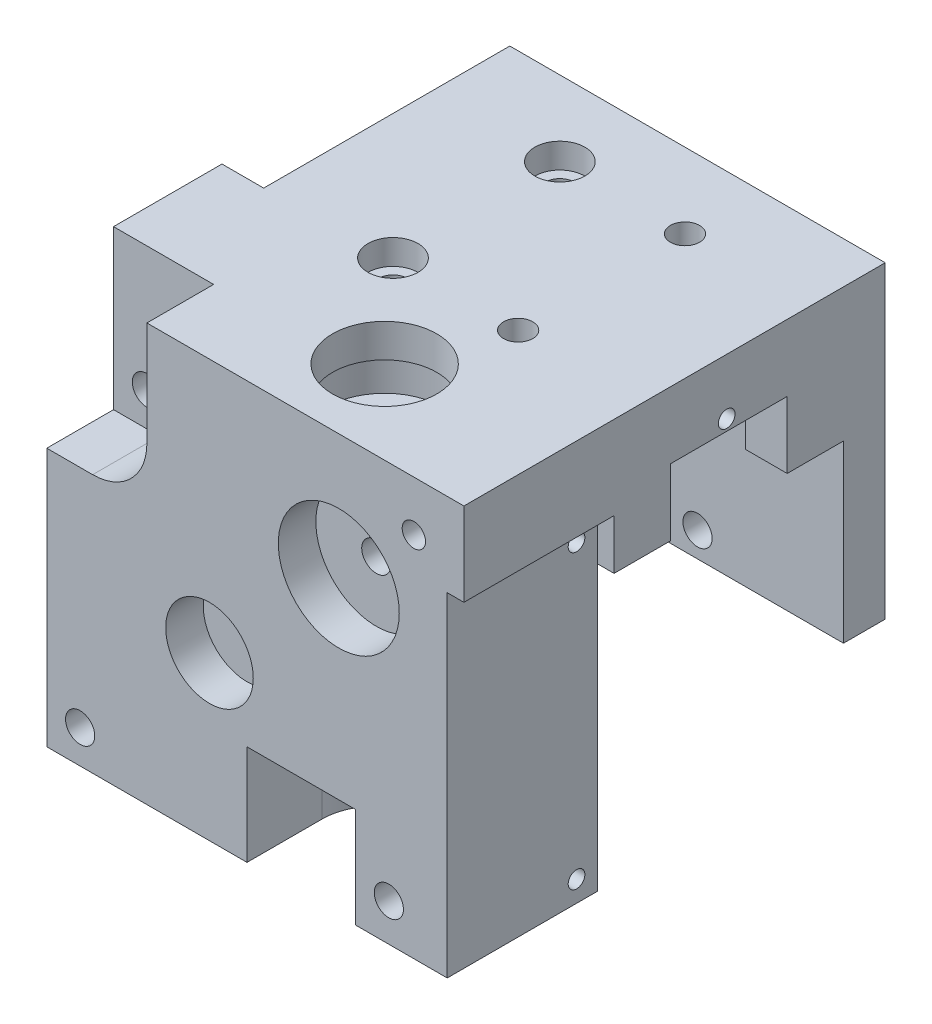
SolidWorks part; units mm, degrees
material "ABS"
ref_plane "Front Plane" through (0, 0, 0) normal (0, 0, 1) x (1, 0, 0)
ref_plane "Top Plane" through (0, 0, 0) normal (0, 1, 0) x (1, 0, 0)
ref_plane "Right Plane" through (0, 0, 0) normal (1, 0, 0) x (0, 0, -1)
sketch "Sketch1" plane through (0, 0, 0) normal (0, 1, 0) x (1, 0, 0)
  line L1 (-17.5, -14) -> (17.5, -14)
  line L2 (-17.5, -14) -> (-17.5, 14)
  line L3 (-17.5, 14) -> (17.5, 14)
  line L4 (17.5, -14) -> (17.5, 14)
  line L5 (-17.5, -14) -> (17.5, 14) construction
  line L6 (-17.5, 14) -> (17.5, -14) construction
  point P0 (0, 0)
  dimension "D1" = 28
  dimension "D2" = 35
extrude "Boss-Extrude1" add sketch "Sketch1" along normal blind 4
sketch "Sketch2" plane through (0, 4, 0) normal (0, 1, 0) x (1, 0, 0)
  line L0 (-17.5, -14) -> (17.5, -14) construction
  line L1 (-17.5, 14) -> (-17.5, -14) construction
  line L2 (-17.5, -14) -> (17.5, -14) construction
  line L3 (17.5, 14) -> (-17.5, 14) construction
  circle A0 centre (-7.5, -10) radius 1.75
  circle A1 centre (-7.5, 10) radius 1.75
  circle A2 centre (7.5, -10) radius 1.75
  circle A3 centre (7.5, 10) radius 1.75
  dimension "D1" = 3.5
  dimension "D2" = 3.5
  dimension "D5" = 3.5
  dimension "D8" = 3.5
  dimension "D3" = 20
  dimension "D4" = 4
  dimension "D6" = 15
  dimension "D7" = 10
  dimension "D9" = 15
  dimension "D10" = 4
  dimension "D11" = 4
extrude "Cut-Extrude1" cut sketch "Sketch2" against normal through all
sketch "Sketch3" plane through (0, 0, 14) normal (0, 0, 1) x (1, 0, 0)
  line L0 (17.5, 4) -> (17.5, 0) construction
  line L1 (-17.5, 4) -> (17.5, 4)
  line L2 (-17.5, 4) -> (-17.5, -46)
  line L3 (-17.5, -46) -> (17.5, -46)
  line L4 (17.5, 4) -> (17.5, -46)
  dimension "D1" = 50
extrude "Boss-Extrude2" add sketch "Sketch3" along normal blind 17.5 and the other way blind 0.5
sketch "Sketch7" plane through (0, 0, -14) normal (0, 0, -1) x (-1, 0, 0)
  line L1 (-17.5, 4) -> (17.5, 4)
  line L2 (-17.5, 4) -> (-17.5, -33)
  line L3 (-17.5, -33) -> (17.5, -33)
  line L4 (17.5, 4) -> (17.5, -33)
  line L6 (17.5, 4) -> (17.5, 0) construction
  dimension "D1" = 37
extrude "Boss-Extrude3" add sketch "Sketch7" along normal blind 5
sketch "Sketch10" plane through (0, 0, -19) normal (0, 0, -1) x (-1, 0, 0)
  line L1 (0, 4) -> (0, -33) construction
  line L3 (17.5, 4) -> (-17.5, 4) construction
  line L4 (-17.5, -33) -> (17.5, -33) construction
  circle A1 centre (-5, -30) radius 1.75
  circle A2 centre (5, -30) radius 1.75
  dimension "D1" = 3
  dimension "D2" = 3.5
  dimension "D4" = 3.5
  dimension "D3" = 5
  dimension "D5" = 5
extrude "Cut-Extrude6" cut sketch "Sketch10" against normal blind 5
sketch "Sketch18" plane through (0, 4, 0) normal (0, 1, 0) x (1, 0, 0)
  line L0 (-17.5, -10) -> (-10.5, -10)
  line L1 (-17.5, 19) -> (-17.5, -31.5) construction
  line L2 (-10.5, -10) -> (-10.5, -11.5)
  line L3 (-10.5, -11.5) -> (-17.5, -11.5)
  line L4 (-17.5, -11.5) -> (-17.5, -10)
  line L5 (17.5, 10) -> (10.5, 10)
  line L6 (17.5, -31.5) -> (17.5, 19) construction
  line L7 (10.5, 10) -> (10.5, 11.5)
  line L8 (10.5, 11.5) -> (17.5, 11.5)
  line L9 (17.5, 11.5) -> (17.5, 10)
  circle A0 centre (-7.5, -10) radius 1.75 construction
  circle A1 centre (7.5, 10) radius 1.75 construction
  dimension "D4" = 3
  dimension "D1" = 0
  dimension "D2" = 3
  dimension "D3" = 1.5
  dimension "D5" = 0
  dimension "D6" = 1.5
extrude "Cut-Extrude14" [suppressed] cut sketch "Sketch18" against normal through all
sketch "Sketch19" plane through (0, 4, 0) normal (0, 1, 0) x (1, 0, 0)
  line L0 (-17.5, 19) -> (-17.5, -31.5) construction
  line L1 (17.5, -31.5) -> (17.5, 19) construction
  circle A0 centre (-7.5, 0) radius 1.75
  circle A1 centre (7.5, 0) radius 1.75
  dimension "D3" = 3.5
  dimension "D4" = 3.5
  dimension "D1" = 10
  dimension "D2" = 10
extrude "Cut-Extrude15" [suppressed] cut sketch "Sketch19" against normal through all
sketch "Sketch20" [suppressed] plane through (0, 0, 0) normal (0, -1, 0) x (1, 0, 0)
  line L1 (10.9641, 0) -> (9.2321, 3)
  line L2 (9.2321, 3) -> (5.7679, 3)
  line L3 (5.7679, 3) -> (4.0359, 0)
  line L4 (4.0359, 0) -> (5.7679, -3)
  line L5 (5.7679, -3) -> (9.2321, -3)
  line L6 (9.2321, -3) -> (10.9641, 0)
  line L7 (-10.9641, 0) -> (-9.2321, -3)
  line L8 (-9.2321, -3) -> (-5.7679, -3)
  line L9 (-5.7679, -3) -> (-4.0359, 0)
  line L10 (-4.0359, 0) -> (-5.7679, 3)
  line L11 (-5.7679, 3) -> (-9.2321, 3)
  line L12 (-9.2321, 3) -> (-10.9641, 0)
  circle A0 centre (7.5, 0) radius 3 construction
  circle A1 centre (-7.5, 0) radius 3 construction
  dimension "D1" = 6
  dimension "D2" = 6
extrude "Cut-Extrude16" [suppressed] cut sketch "Sketch20" against normal blind 3
sketch "Sketch21" [suppressed] plane through (0, 4, 0) normal (0, 1, 0) x (1, 0, 0)
  line L0 (-10.5, -10) -> (-17.5, -10) construction
  circle A0 centre (-17, -10) radius 0.5
  dimension "D1" = 1
extrude "Cut-Extrude17" [suppressed] cut sketch "Sketch21" against normal blind 4
pattern_linear "LPattern2" [suppressed] count 4 spacing 2 of bodies 121
fillet "Fillet2" [suppressed] radius 0.15
sketch "Sketch24" plane through (-17.5, 0, 0) normal (-1, 0, 0) x (0, 0, 1)
  line L5 (31.5, -46) -> (13.5, -46) construction
  line L6 (13.5, -46) -> (31.5, -46)
  line L7 (13.5, -46) -> (13.5, 0)
  line L8 (13.5, 0) -> (31.5, 0)
  line L9 (31.5, -46) -> (31.5, 0)
  line L10 (13.5, 0) -> (13.5, -46) construction
  line L11 (31.5, 4) -> (31.5, -46) construction
extrude "Boss-Extrude4" add sketch "Sketch24" along normal blind 10
sketch "Sketch37" plane through (-17.5, 0, 0) normal (-1, 0, 0) x (0, 0, 1)
  line L1 (10.5, 4) -> (23.5, 4)
  line L2 (10.5, 4) -> (10.5, -10)
  line L3 (10.5, -10) -> (23.5, -10)
  line L4 (23.5, 4) -> (23.5, -10)
  dimension "D1" = 3
  dimension "D2" = 10
  dimension "D3" = 14
extrude "Boss-Extrude9" add sketch "Sketch37" along normal blind 10
sketch "Sketch22" plane through (0, 0, 31.5) normal (0, 0, 1) x (1, 0, 0)
  line L0 (-27.5, -46) -> (-27.5, 0) construction
  line L1 (-15.5, 0) -> (-27.5, 0)
  line L2 (-27.5, -46) -> (17.5, -46) construction
  line L4 (-27.5, 0) -> (-17.5, 0) construction
  line L5 (-27.5, -46) -> (17.5, -46) construction
  line L6 (-27.5, 0) -> (-27.5, -15)
  line L9 (-27.5, -15) -> (-22, -15)
  line L10 (-15.5, 0) -> (-15.5, -8.5)
  line L11 (9.5, -46) -> (-3.5, -46)
  line L12 (9.5, -46) -> (9.5, -34)
  line L13 (9.5, -34) -> (-3.5, -34)
  line L14 (-3.5, -46) -> (-3.5, -34)
  line L16 (-15.5, 0) -> (-17.5, 0)
  line L17 (-15.5, 0) -> (-15.5, 4)
  line L18 (-15.5, 4) -> (-17.5, 4)
  line L19 (-17.5, 0) -> (-17.5, 4)
  circle A0 centre (-23.5, -42) radius 1.75
  circle A1 centre (13.5, -41.5) radius 1.75
  circle A3 centre (7.5, -11) radius 7.25
  circle A4 centre (-8, -26.5) radius 5.25
  arc A5 (-22, -15) -> (-15.5, -8.5) centre (-22, -8.5) ccw
  circle A6 centre (7.5, -11) radius 1.75
  circle A7 centre (-23.5, -11) radius 1.75
  point P21 (-15.5, -15)
  line M3 (-17.5, 4) -> (-17.5, 0)
  line M6 (17.5, 4) -> (-17.5, 4)
  line M24 (-17.5, 0) -> (-27.5, 0)
  line M25 (-27.5, 0) -> (-27.5, -46)
  dimension "D3" = 3.5
  dimension "D6" = 35
  dimension "D7" = 3.5
  dimension "D9" = 14.5
  dimension "D11" = 10.5
  dimension "D15" = 6.5
  dimension "D22" = 3.5
  dimension "D23" = 3.5
  dimension "D2" = 4
  dimension "D4" = 4.5
  dimension "D5" = 4
  dimension "D8" = 12
  dimension "D10" = 35
  dimension "D12" = 19.5
  dimension "D13" = 19.5
  dimension "D14" = 31
  dimension "D16" = 24
  dimension "D17" = 13
  dimension "D18" = 12
  dimension "D19" = 41
  dimension "D20" = 4
  dimension "D21" = 35
extrude "Cut-Extrude19" cut sketch "Sketch22" against normal up to next contours A0 | A1 | A7 | A6 region at (-23.5, -42, 31.5) region at (13.5, -41.5, 31.5) region at (7.5, -11, 31.5) region at (-23.5, -11, 31.5)
extrude "Cut-Extrude20" cut sketch "Sketch22<3>" against normal blind 4.5 contours A3 | A4
sketch "Sketch22<3>" plane through (0, 0, 31.5) normal (0, 0, 1) x (1, 0, 0) same geometry as "Sketch22"
extrude "Cut-Extrude24" cut sketch "Sketch22<5>" against normal blind 8 contours L9 A5 L10 L1 A7 M24 M25 | L1 L17 M6 M3 region at (-21.6364, -6.9513, 31.5) region at (-16.5, 2, 31.5)
sketch "Sketch22<5>" plane through (0, 0, 31.5) normal (0, 0, 1) x (1, 0, 0) same geometry as "Sketch22"
extrude "Cut-Extrude21" cut sketch "Sketch22<4>" against normal blind 15.5 contours L14 L13 L12 L11
sketch "Sketch22<4>" plane through (0, 0, 31.5) normal (0, 0, 1) x (1, 0, 0) same geometry as "Sketch22"
fillet "Fillet3" radius 6.5 2 edges at (9.5, -40, 16) (-3.5, -40, 16)
sketch "Sketch26" plane through (0, -34, 0) normal (0, -1, 0) x (1, 0, 0)
  line L0 (9.5, 31.5) -> (-3.5, 31.5) construction
  line L1 (-3.5, 22.5) -> (-3.5, 31.5) construction
  circle A0 centre (3, 21.5) radius 2.25
  dimension "D1" = 4.5
  dimension "D2" = 10
  dimension "D3" = 6.5
extrude "Cut-Extrude22" cut sketch "Sketch26" against normal through all
sketch "Sketch27" plane through (0, 4, 0) normal (0, 1, 0) x (1, 0, 0)
  circle A0 centre (3, -21.5) radius 6.25
  dimension "D1" = 12.5
extrude "Cut-Extrude23" cut sketch "Sketch27" against normal blind 8
sketch "Sketch41" plane through (-27.5, 0, 0) normal (-1, 0, 0) x (0, 0, 1)
  line L0 (13.5, -10) -> (13.5, -46) construction
  line L1 (13.5, -46) -> (31.5, -46) construction
  line L2 (20.5, -42.5) -> (20.5, -39)
  line L15 (23, -42.5) -> (23, -39)
  line L16 (17, -46) -> (17, -48.5)
  line L17 (20.5, -39) -> (23, -39)
  line L18 (17, -46) -> (21.8734, -46)
  circle A0 centre (17, -42.5) radius 1.25
  arc A1 (17, -46) -> (20.5, -42.5) centre (17, -42.5) ccw
  arc A2 (17, -48.5) -> (23, -42.5) centre (17, -42.5) ccw
  line M16 (13.5, -46) -> (31.5, -46)
  dimension "D5" = 2.5
  dimension "D1" = 3.5
  dimension "D2" = 3.5
  dimension "D3" = 3.5
  dimension "D4" = 2.5
extrude "Boss-Extrude10" [suppressed] add sketch "Sketch41" along normal blind 2.5 contours A0 | A2 L15 L17 L2 A1 M16
sketch "Sketch43" plane through (17.5, 0, 0) normal (1, 0, 0) x (0, 0, -1)
  line L0 (-31.5, -46) -> (-31.5, 4)
  line L1 (-31.5, 4) -> (19, 4)
  line L2 (19, 4) -> (19, -33)
  line L3 (19, -33) -> (14, -33)
  line L6 (-13.5, 0) -> (14, 0) construction
  line L7 (-31.5, -46) -> (-13.5, -46)
  line L11 (-6.75, -4) -> (-6.75, -12)
  line L12 (-6.75, -12) -> (-13.5, -12)
  line L13 (7.25, -4) -> (7.25, -12)
  line L14 (7.25, -12) -> (14, -12)
  line L15 (-6.75, -4) -> (7.25, -4)
  line L16 (-13.5, -12) -> (-13.5, -46)
  line L17 (14, -12) -> (14, -33)
  dimension "D1" = 29
  dimension "D3" = 6.75
  dimension "D4" = 12
  dimension "D5" = 14
extrude "Boss-Extrude11" add sketch "Sketch43" along normal blind 5
sketch "Sketch44" plane through (-17.5, 0, 0) normal (-1, 0, 0) x (0, 0, 1)
  line L0 (10.5, 4) -> (-19, 4)
  line L1 (-19, 4) -> (-19, -33)
  line L2 (-19, -33) -> (-14, -33)
  line L8 (-14, -33) -> (-14, -12)
  line L9 (-14, -12) -> (-7.25, -12)
  line L10 (-7.25, -12) -> (-7.25, -4)
  line L11 (-7.25, -4) -> (6.75, -4)
  line L12 (6.75, -4) -> (6.75, -12)
  line L16 (6.75, -12) -> (13.5, -12)
  line L17 (13.5, -12) -> (13.5, -10)
  line L18 (13.5, -10) -> (10.5, -10)
  line L19 (10.5, -10) -> (10.5, 4)
extrude "Boss-Extrude12" add sketch "Sketch44" along normal blind 5
sketch "Sketch29" plane through (0, 0, 13.5) normal (0, 0, -1) x (-1, 0, 0)
  line L1 (-4.1514, -11) -> (-5.8257, -8.1)
  line L2 (-5.8257, -8.1) -> (-9.1743, -8.1)
  line L3 (-9.1743, -8.1) -> (-10.8486, -11)
  line L4 (-10.8486, -11) -> (-9.1743, -13.9)
  line L5 (-9.1743, -13.9) -> (-5.8257, -13.9)
  line L6 (-5.8257, -13.9) -> (-4.1514, -11)
  line L7 (20.1514, -11) -> (21.8257, -13.9)
  line L8 (21.8257, -13.9) -> (25.1743, -13.9)
  line L9 (25.1743, -13.9) -> (26.8486, -11)
  line L10 (26.8486, -11) -> (25.1743, -8.1)
  line L11 (25.1743, -8.1) -> (21.8257, -8.1)
  line L12 (21.8257, -8.1) -> (20.1514, -11)
  line L13 (-10.1514, -41.5) -> (-11.8257, -38.6)
  line L14 (-11.8257, -38.6) -> (-15.1743, -38.6)
  line L15 (-15.1743, -38.6) -> (-16.8486, -41.5)
  line L16 (-16.8486, -41.5) -> (-15.1743, -44.4)
  line L17 (-15.1743, -44.4) -> (-11.8257, -44.4)
  line L18 (-11.8257, -44.4) -> (-10.1514, -41.5)
  line L25 (23.5, -45.3486) -> (26.4, -43.6743)
  line L26 (26.4, -43.6743) -> (26.4, -40.3257)
  line L27 (26.4, -40.3257) -> (23.5, -38.6514)
  line L28 (23.5, -38.6514) -> (20.6, -40.3257)
  line L29 (20.6, -40.3257) -> (20.6, -43.6743)
  line L30 (20.6, -43.6743) -> (23.5, -45.3486)
  circle A0 centre (-7.5, -11) radius 2.9 construction
  circle A1 centre (23.5, -11) radius 2.9 construction
  circle A2 centre (-13.5, -41.5) radius 2.9 construction
  circle A3 centre (23.5, -42) radius 2.9 construction
  dimension "D1" = 5.8
  dimension "D2" = 5.8
  dimension "D3" = 5.8
  dimension "D4" = 5.8
extrude "Cut-Extrude25" cut sketch "Sketch29" against normal blind 3 and the other way up to surface (6.75 mm away) other way up to face at (-20, -8, 6.75)
sketch "Sketch30" plane through (0, 4, 0) normal (0, 1, 0) x (1, 0, 0)
  circle A0 centre (-7.5, 10) radius 3
  circle A1 centre (-7.5, -10) radius 3
  dimension "D1" = 6
  dimension "D2" = 6
extrude "Cut-Extrude26" cut sketch "Sketch30" against normal blind 3
ref_plane "Plane1" [suppressed] through (0, 0, 0) normal (-1, 0, 0) x (0, 0, 1)
sketch "Sketch38" plane through (0, -4, 0) normal (0, 1, 0) x (1, 0, 0)
  circle A0 centre (3, -21.5) radius 7
  dimension "D1" = 14
extrude "Cut-Extrude31" cut sketch "Sketch38" along normal blind 4
sketch "Sketch39" plane through (-27.5, 0, 0) normal (-1, 0, 0) x (0, 0, 1)
  line L0 (13.5, -46) -> (17, -46)
  line L1 (13.5, -46) -> (31.5, -46) construction
  line L2 (13.5, -46) -> (13.5, -19)
  line L3 (13.5, -10) -> (13.5, -46) construction
  line L4 (13.5, -19) -> (17, -19)
  line L5 (20.5, -22.5) -> (20.5, -26)
  line L6 (20.5, -26) -> (27.5, -26)
  line L7 (27.5, -26) -> (27.5, -39)
  line L8 (27.5, -39) -> (20.5, -39)
  line L9 (20.5, -39) -> (20.5, -42.5)
  line L11 (27.5, -29) -> (23.5, -29)
  line L12 (27.5, -29) -> (27.5, -36)
  line L13 (27.5, -36) -> (23.5, -36)
  line L14 (23.5, -29) -> (23.5, -36)
  line L15 (13.5, -26) -> (18.5, -26)
  line L16 (13.5, -26) -> (13.5, -39)
  line L17 (13.5, -39) -> (18.5, -39)
  line L18 (18.5, -26) -> (18.5, -39)
  arc A0 (17, -46) -> (20.5, -42.5) centre (17, -42.5) ccw
  arc A1 (17, -19) -> (20.5, -22.5) centre (17, -22.5) cw
  point P15 (20.5, -46)
  point P18 (20.5, -19)
  dimension "D7" = 3.5
  dimension "D1" = 7
  dimension "D2" = 27
  dimension "D3" = 7
  dimension "D4" = 7
  dimension "D5" = 7
  dimension "D6" = 13
  dimension "D8" = 4
  dimension "D9" = 7
  dimension "D10" = 3
  dimension "D11" = 5
extrude "Cut-Extrude32" cut sketch "Sketch39" against normal blind 3 contours L18 L15 L2 L17 | L11 L14 L13 L7 region at (-27.5, -32.5, 16) region at (-27.5, -32.5, 25.5)
sketch "Sketch40" plane through (-27.5, 0, 0) normal (-1, 0, 0) x (0, 0, 1)
  line L0 (13.5, -10) -> (13.5, -26) construction
  line L1 (13.5, -46) -> (31.5, -46) construction
  circle A0 centre (17, -22.5) radius 1.4
  dimension "D3" = 2.8
  dimension "D1" = 3.5
  dimension "D2" = 23.5
extrude "Cut-Extrude33" cut sketch "Sketch40" against normal blind 15
sketch "Sketch42" plane through (0, 0, 31.5) normal (0, 0, 1) x (1, 0, 0)
  circle A0 centre (16.5, -2) radius 1.4
  circle A1 centre (-23.5, -42) radius 1.75 construction
  dimension "D3" = 2.8
  dimension "D1" = 40
  dimension "D2" = 40
extrude "Cut-Extrude34" cut sketch "Sketch42" against normal blind 10
sketch "Sketch45" plane through (22.5, 0, 0) normal (1, 0, 0) x (0, 0, -1)
  line L0 (-13.5, 0) -> (14, 0) construction
  circle A0 centre (0, -2.7) radius 1
  dimension "D2" = 2
  dimension "D1" = 2.7
extrude "Cut-Extrude35" cut sketch "Sketch45" against normal through all
sketch "Sketch46" plane through (-27.5, 0, 0) normal (-1, 0, 0) x (0, 0, 1)
  line L0 (13.5, -39) -> (13.5, -46) construction
  line L1 (13.5, -46) -> (31.5, -46) construction
  circle A0 centre (17, -42.5) radius 1.5
  dimension "D3" = 3
  dimension "D1" = 3.5
  dimension "D2" = 3.5
extrude "Boss-Extrude13" add sketch "Sketch46" along normal blind 2.5
sketch "Sketch48" plane through (22.5, 0, 0) normal (1, 0, 0) x (0, 0, -1)
  line L0 (-31.5, 4) -> (-31.5, -46) construction
  line L1 (-13.5, -46) -> (-31.5, -46)
  line L2 (-13.5, -46) -> (-13.5, -6)
  line L3 (-13.5, -6) -> (-31.5, -6)
  line L4 (-31.5, -46) -> (-31.5, -6)
  dimension "D1" = 40
extrude "Cut-Extrude36" cut sketch "Sketch48" against normal blind 2
sketch "Sketch49" plane through (20.5, 0, 0) normal (1, 0, 0) x (0, 0, -1)
  line L0 (-31.5, -46) -> (-13.5, -46) construction
  line L1 (-13.5, -46) -> (-13.5, -12) construction
  circle A0 centre (-16, -43.5) radius 1
  circle A1 centre (-16, -8.5) radius 1
  dimension "D3" = 2
  dimension "D5" = 2
  dimension "D1" = 2.5
  dimension "D2" = 2.5
  dimension "D4" = 35
extrude "Cut-Extrude37" cut sketch "Sketch49" against normal blind 10
sketch "Sketch47" plane through (0, 4, 0) normal (0, 1, 0) x (1, 0, 0)
  line L0 (-22.5, -10.5) -> (-22.5, 19) construction
  line L1 (-2.5, 5.4692) -> (-22.5, 5.4692)
  line L2 (-2.5, 5.4692) -> (-2.5, -4.5308)
  line L3 (-2.5, -4.5308) -> (-22.5, -4.5308)
  line L4 (-22.5, 5.4692) -> (-22.5, -4.5308)
  line L5 (-2.5, 5.4692) -> (-22.5, -4.5308) construction
  line L6 (-2.5, -4.5308) -> (-22.5, 5.4692) construction
  point P0 (-12.5, 0.4692)
  dimension "D1" = 20
  dimension "D2" = 10
